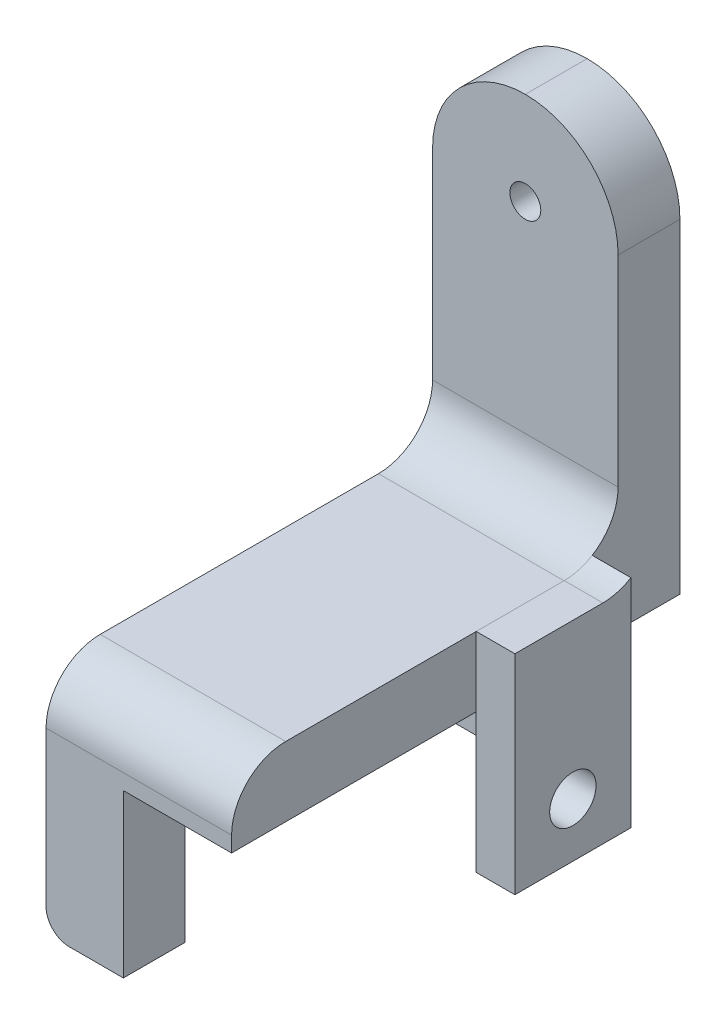
SolidWorks part; units mm, degrees
ref_plane "Front Plane" through (0, 0, 0) normal (0, 0, 1) x (1, 0, 0)
ref_plane "Top Plane" through (0, 0, 0) normal (0, 1, 0) x (1, 0, 0)
ref_plane "Right Plane" through (0, 0, 0) normal (1, 0, 0) x (0, 0, -1)
sketch "Sketch2" plane through (0, -0.0002, -27.9978) normal (0, 0, -1) x (1, 0, 0)
  line L1 (45.1952, -27.127) -> (69.1952, -27.127)
  line L2 (45.1952, -27.127) -> (45.1952, 47.873)
  line L3 (45.1952, 47.873) -> (69.1952, 47.873)
  line L4 (69.1952, -27.127) -> (69.1952, 47.873)
  dimension "D4" = 75
extrude "Boss-Extrude1" add sketch "Sketch2" along normal blind 8
fillet "Fillet1" radius 12 2 edges at (45.1952, 27.1268, -31.9981) (69.1952, 27.1268, -31.9981)
sketch "Sketch3" plane through (0, -0.0002, -27.9978) normal (0, 0, 1) x (1, 0, 0)
  line L0 (69.1952, 15.127) -> (69.1952, -47.873) construction
  line L1 (45.1952, -47.873) -> (69.1952, -47.873)
  line L2 (45.1952, -47.873) -> (45.1952, -17.873)
  line L3 (45.1952, -17.873) -> (69.1952, -17.873)
  line L4 (69.1952, -47.873) -> (69.1952, -17.873)
  dimension "D1" = 30
extrude "Boss-Extrude2" add sketch "Sketch3" along normal blind 50
sketch "Sketch4" plane through (69.1952, 0, 0) normal (1, 0, 0) x (0, 0, -1)
  line L2 (27.9977, -54.1007) -> (27.9977, -26.8732)
  line L3 (27.9977, -26.8732) -> (-14.0023, -26.8732)
  line L4 (-14.0023, -54.1007) -> (-14.0023, -26.8732)
  line L5 (-22.0023, -17.8728) -> (35.9977, -17.8728) construction
  line L6 (35.998, 15.1267) -> (35.9975, -47.8733) construction
  line L7 (6.9977, -17.8728) -> (6.9977, -54.1007) construction
  line L8 (27.9977, -54.1007) -> (-14.0023, -54.1007)
  dimension "D1" = 21
  dimension "D2" = 42
extrude "Cut-Extrude1" cut sketch "Sketch4" against normal up to surface (24 mm away) up to face at (45.1952, -16.8731, -13.9977)
fillet "Fillet2" radius 7 2 edges at (57.1952, -17.8728, 22.0023) (57.1952, -17.8732, -27.9977)
sketch "Sketch5" plane through (69.1952, 0, 0) normal (1, 0, 0) x (0, 0, -1)
  line L10 (-22.0025, -47.8728) -> (-22.0024, -24.8728) construction
  line L11 (35.998, 15.1267) -> (35.9975, -47.8733) construction
  line L20 (20.9977, -17.8732) -> (-15.0023, -17.8729)
  line L21 (-22.0024, -24.8728) -> (-22.0025, -47.8728)
  line L22 (-22.0025, -47.8728) -> (-14.0023, -47.8729)
  line L23 (-14.0023, -47.8729) -> (-14.0023, -26.8732)
  line L24 (-14.0023, -26.8732) -> (27.9977, -26.8732)
  line L25 (27.9977, -26.8732) -> (27.9977, -47.8732)
  line L26 (27.9977, -47.8732) -> (35.9975, -47.8733)
  line L27 (35.9975, -47.8733) -> (35.998, 15.1267)
  line L28 (35.998, 15.1267) -> (27.998, 15.1268)
  line L29 (27.998, 15.1268) -> (27.9978, -10.8732)
  line L31 (-22.0024, -26.8732) -> (-22.0025, -47.8728)
  line L32 (-22.0025, -47.8728) -> (35.9975, -47.8733)
  line L34 (-22.0024, -26.8732) -> (35.9976, -26.8732)
  line L37 (35.9975, -47.8733) -> (35.9976, -26.8732)
  arc A2 (-15.0023, -17.8729) -> (-22.0024, -24.8728) centre (-15.0024, -24.8729) ccw
  arc A3 (20.9977, -17.8732) -> (27.9978, -10.8732) centre (20.9978, -10.8732) ccw
  dimension "D1" = 0
extrude "Cut-Extrude3" cut sketch "Sketch5" against normal blind 14
sketch "Sketch6" plane through (69.1952, 0, 0) normal (1, 0, 0) x (0, 0, -1)
  line L0 (6.9976, -26.8732) -> (6.9976, -51.8245) construction
  line L1 (35.9976, -26.8732) -> (-22.0024, -26.8732) construction
  line L2 (1.5238, -51.8245) -> (14.5238, -51.8245) construction
  line L3 (-15.0023, -17.8729) -> (20.9977, -17.8732) construction
  line L4 (21.0341, -17.8731) -> (9.6476, -17.8731)
  line L5 (24.6476, -16.8463) -> (24.6476, -44.8732)
  line L6 (24.6476, -44.8732) -> (9.6476, -44.8732)
  line L7 (9.6476, -17.8731) -> (9.6476, -44.8732)
  circle A0 centre (-3.1523, -37.8732) radius 3 construction
  circle A1 centre (17.1476, -37.8732) radius 3
  arc A2 (20.9977, -17.8732) -> (27.9978, -10.8732) centre (20.9978, -10.8732) ccw construction
  arc A3 (21.0341, -17.8731) -> (24.6476, -16.8463) centre (20.9978, -10.8732) ccw
  point P15 (24.6476, -17.1192)
  point P16 (0, 0)
  point P23 (24.6476, -16.8463)
  dimension "D1" = 15
  dimension "D2" = 7.5
  dimension "D3" = 7
extrude "Boss-Extrude3" add sketch "Sketch6" along normal blind 5
fillet "Fillet3" radius 3 2 edges at (45.1952, -47.8728, 18.0024) (45.1952, -47.8732, -31.9976)
sketch "Sketch7" plane through (0, -0.0002, -27.9978) normal (0, 0, 1) x (1, 0, 0)
  line L0 (57.1952, 27.127) -> (57.1952, 15.127) construction
  arc A0 (69.1952, 15.127) -> (57.1952, 27.127) centre (57.1952, 15.127) ccw construction
  arc A1 (69.1952, 15.127) -> (57.1952, 27.127) centre (57.1952, 15.127) ccw construction
  circle A2 centre (57.1952, 15.127) radius 2
extrude "Cut-Extrude4" cut sketch "Sketch7" against normal through all
sketch "Sketch8" plane through (0, -0.0003, -35.9978) normal (0, 0, -1) x (-1, 0, 0)
  circle A0 centre (-57.1952, 15.127) radius 3
extrude "Cut-Extrude5" cut sketch "Sketch8" against normal blind 4
